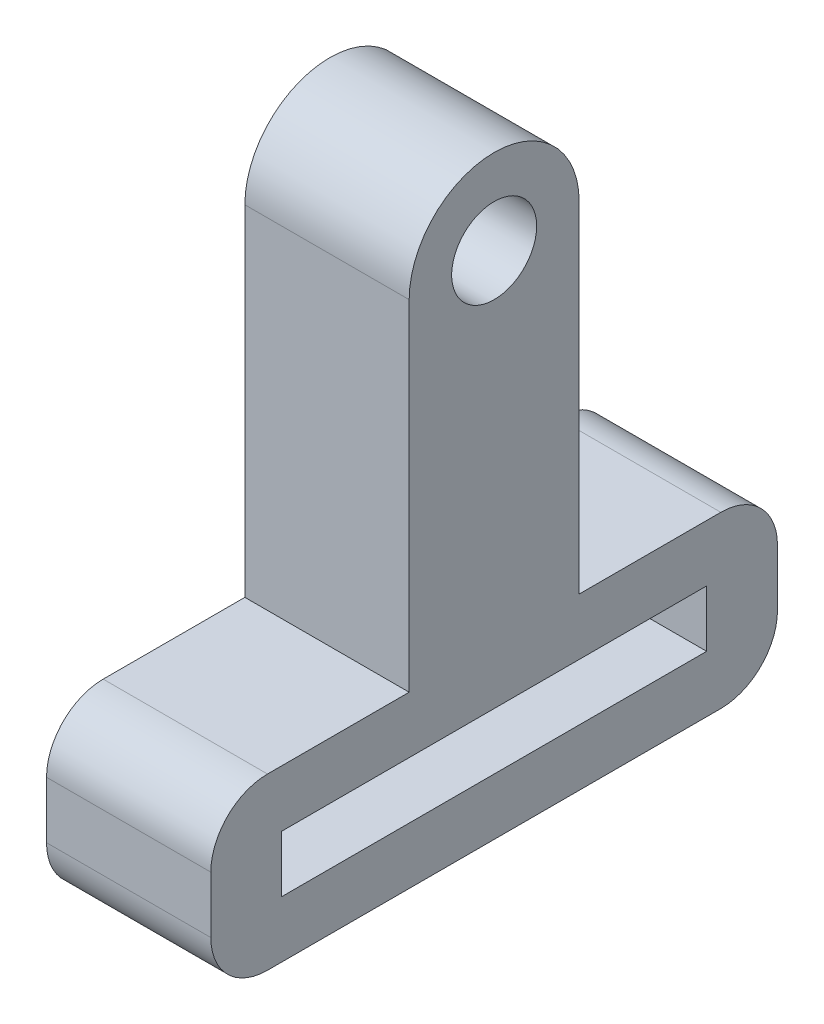
SolidWorks part; units mm, degrees
ref_plane "Alzado" through (0, 0, 0) normal (0, 0, 1) x (1, 0, 0)
ref_plane "Planta" through (0, 0, 0) normal (0, 1, 0) x (1, 0, 0)
ref_plane "Vista lateral" through (0, 0, 0) normal (1, 0, 0) x (0, 0, -1)
sketch "Croquis1" plane through (0, 0, 0) normal (1, 0, 0) x (0, 0, -1)
  line L2 (-10, 1) -> (-10, -1)
  line L3 (-8, -3) -> (8, -3)
  line L4 (10, 1) -> (10, -1)
  line L5 (-10, 3) -> (10, -3) construction
  line L6 (-10, -3) -> (10, 3) construction
  line L7 (-7.5, 1) -> (7.5, 1)
  line L8 (-7.5, 1) -> (-7.5, -1)
  line L9 (-7.5, -1) -> (7.5, -1)
  line L10 (7.5, 1) -> (7.5, -1)
  line L11 (-7.5, 1) -> (7.5, -1) construction
  line L12 (-7.5, -1) -> (7.5, 1) construction
  line L15 (-10, 3) -> (10, 3) construction
  line L27 (-3, 3) -> (-8, 3)
  line L28 (3, 3) -> (8, 3)
  line L35 (0, 3) -> (0, 15) construction
  line L36 (-3, 15) -> (-3, 3)
  line L39 (3, 15) -> (3, 3)
  circle A1 centre (0, 15) radius 1.5
  arc A2 (3, 15) -> (-3, 15) centre (0, 15) ccw
  arc A3 (8, -3) -> (10, -1) centre (8, -1) ccw
  arc A4 (8, 3) -> (10, 1) centre (8, 1) cw
  arc A5 (-10, -1) -> (-8, -3) centre (-8, -1) ccw
  arc A6 (-8, 3) -> (-10, 1) centre (-8, 1) ccw
  point P0 (0, 0)
  point P6 (0, 0)
  dimension "D18" = 6
  dimension "D17" = 3
  dimension "D6" = 2
  dimension "D2" = 20
  dimension "D3" = 2
  dimension "D4" = 15
  dimension "D5" = 6
  dimension "D16" = 12
  dimension "D23" = 2
extrude "Saliente-Extruir1" add sketch "Croquis1" along normal mid plane 5.8
